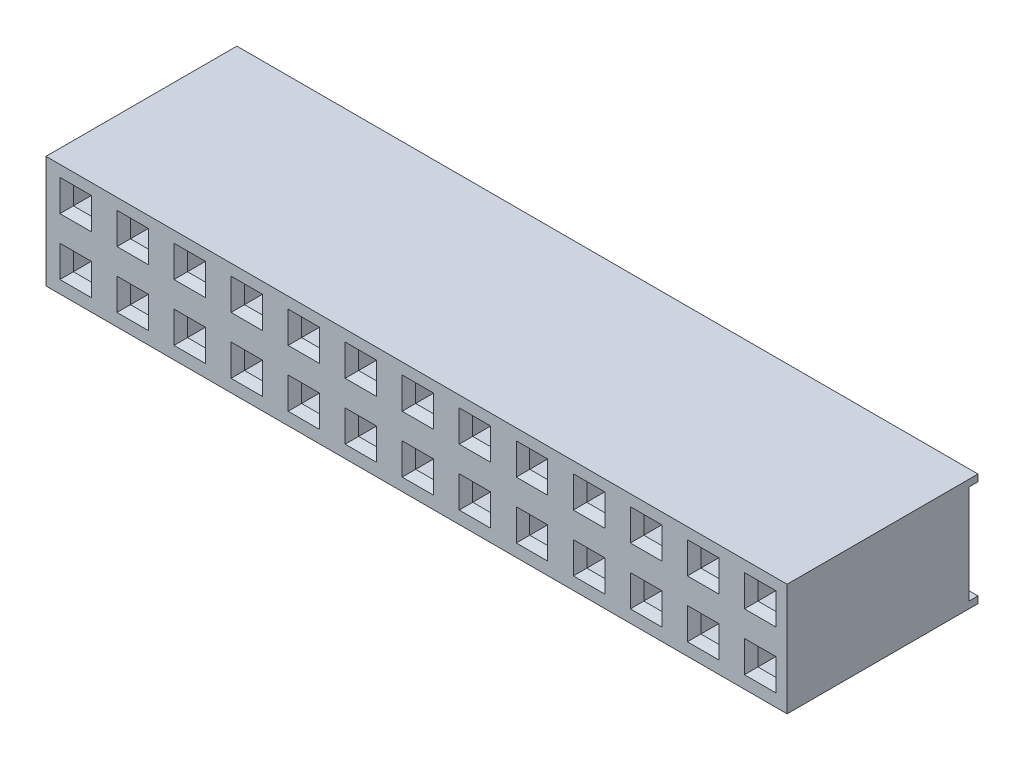
SolidWorks part; units mm, degrees
material "ABS"
ref_plane "Front Plane" through (0, 0, 0) normal (0, 0, 1) x (1, 0, 0)
ref_plane "Top Plane" through (0, 0, 0) normal (0, 1, 0) x (1, 0, 0)
ref_plane "Right Plane" through (0, 0, 0) normal (1, 0, 0) x (0, 0, -1)
sketch "Sketch1" plane through (0, 0, 0) normal (1, 0, 0) x (0, 0, -1)
  line L16 (8.5, 5) -> (0, 5)
  line L17 (0, 5) -> (0, 0)
  line L18 (0, 0) -> (8.5, 0)
  line L19 (8.5, 0) -> (8.5, 0.3)
  line L20 (8.5, 0.3) -> (8.1, 0.3)
  line L21 (8.1, 0.3) -> (8.1, 4.7)
  line L22 (8.1, 4.7) -> (8.5, 4.7)
  line L23 (8.5, 4.7) -> (8.5, 5)
  dimension "D2" = 0.3
  dimension "D3" = 0.4
  dimension "D4" = 8.5
  dimension "D5" = 5
extrude "Boss-Extrude1" add sketch "Sketch1" against normal blind 33 separate body
sketch "Sketch2" plane through (0, 0, -8.1) normal (0, 0, -1) x (-1, 0, 0)
  line L0 (33, 5) -> (0, 5) construction
  line L3 (2, 3.6) -> (2, 4.2)
  line L4 (2, 3.6) -> (0.4, 3.6)
  line L5 (0.4, 3.6) -> (0.4, 4.2)
  line L6 (2, 4.2) -> (0.4, 4.2)
  line L8 (0, 0.3) -> (0, 4.7) construction
  dimension "D1" = 0.6
  dimension "D2" = 0.4
  dimension "D3" = 1.6
  dimension "D4" = 0.8
extrude "Cut-Extrude1" cut sketch "Sketch2" against normal blind 2
sketch "Sketch3" plane through (0, 0, 0) normal (0, 0, -1) x (-1, 0, 0)
  line L1 (2, 4.2) -> (0.4, 4.2) construction
  line L4 (0.8, 4.2) -> (1.6, 4.2)
  line L5 (0.8, 3.4) -> (0.8, 4.2)
  line L6 (1.6, 3.4) -> (0.8, 3.4)
  line L7 (1.6, 4.2) -> (1.6, 3.4)
  point P4 (1.2, 4.2)
  dimension "D1" = 0.8
extrude "Cut-Extrude2" cut sketch "Sketch3" along normal blind 2.5
sketch "Sketch4" plane through (0, 0, 0) normal (0, 0, 1) x (1, 0, 0)
  line L4 (-0.5, 4.5) -> (-1.9, 4.5)
  line L5 (-0.5, 4.5) -> (-1.9, 4.5)
  line L31 (-0.5, 3.1) -> (-0.5, 4.5)
  line L32 (-1.9, 3.1) -> (-0.5, 3.1)
  line L33 (-1.9, 4.5) -> (-1.9, 3.1)
  line L35 (-0.5, 3.1) -> (-0.5, 4.5)
  line L36 (-1.9, 3.1) -> (-0.5, 3.1)
  line L37 (-1.9, 4.5) -> (-1.9, 3.1)
  dimension "D1" = 0.3
extrude "Cut-Extrude3" cut sketch "Sketch4" against normal blind 0.5 draft 45
pattern_linear "LPattern1" count 17 spacing 2.54 along (-1, 0, 0) count 3 spacing 2.54 along (0, -1, 0) of "Cut-Extrude2", "Cut-Extrude1", "Cut-Extrude3"
equation "\"Pin Number\"= 20"
equation "\"Pitch\"=2.54"
equation "\"D4@LPattern1\" = \"Pitch\""
equation "\"D3@LPattern1\" = \"Pitch\""
equation "\"D2@LPattern1\" = \"Pitch\""
equation "\"D1@LPattern1\" = \"Pin Number\" / 2"
equation "\"Pin Number\"= \"D1@Boss-Extrude1\""
